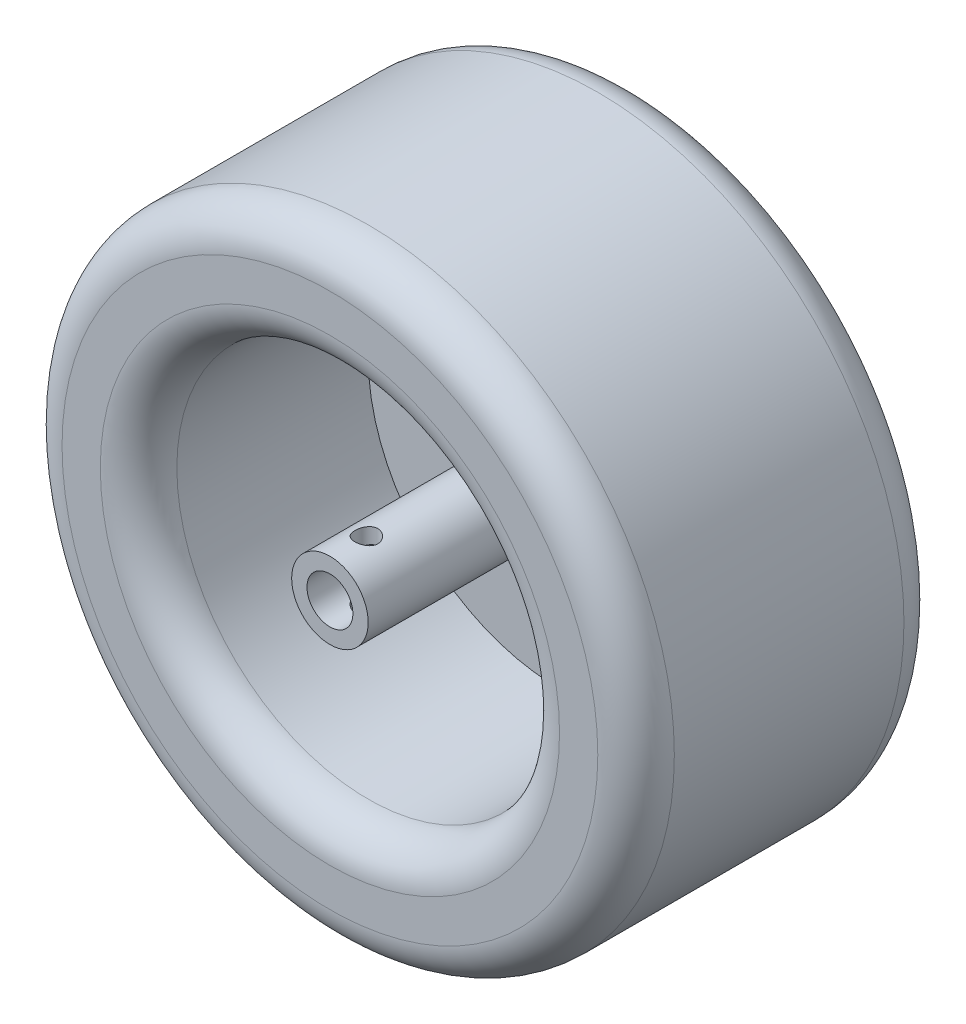
SolidWorks part; units mm, degrees
ref_plane "Front Plane" through (0, 0, 0) normal (0, 0, 1) x (1, 0, 0)
ref_plane "Top Plane" through (0, 0, 0) normal (0, 1, 0) x (1, 0, 0)
ref_plane "Right Plane" through (0, 0, 0) normal (1, 0, 0) x (0, 0, -1)
sketch "Sketch1" plane through (0, 0, 0) normal (0, 0, 1) x (1, 0, 0)
  circle A0 centre (0, 0) radius 40
  circle A1 centre (0, 0) radius 25
  dimension "D1" = 80
  dimension "D2" = 15
extrude "Boss-Extrude1" add sketch "Sketch1" along normal blind 35
sketch "Sketch2" plane through (0, 0, 0) normal (0, 0, -1) x (-1, 0, 0)
  circle A0 centre (0, 0) radius 40
  dimension "D1" = 80
extrude "Boss-Extrude2" add sketch "Sketch2" against normal blind 5
sketch "Sketch4" plane through (0, 0, 0) normal (0, 0, -1) x (-1, 0, 0)
  circle A0 centre (0, 0) radius 30
  circle A1 centre (0, 0) radius 40
  dimension "D1" = 60
  dimension "D2" = 80
extrude "Boss-Extrude3" add sketch "Sketch4" along normal blind 5
sketch "Sketch6" plane through (0, 0, 5) normal (0, 0, 1) x (1, 0, 0)
  circle A0 centre (0, 0) radius 5
  circle A1 centre (0, 0) radius 3
  dimension "D1" = 10
  dimension "D2" = 2
extrude "hub" add sketch "Sketch6" along normal blind 30
fillet "Fillet1 design" radius 5 4 edges at (-40, 0, -5) (-30, 0, -5) (40, 0, 35) (25, 0, 35)
sketch "Sketch8" plane through (0, 0, 0) normal (0, 1, 0) x (1, 0, 0)
  circle A0 centre (0, -30.2431) radius 1.5
  dimension "D1" = 3
extrude "hub holes" cut sketch "Sketch8" against normal blind 10 and the other way blind 10
